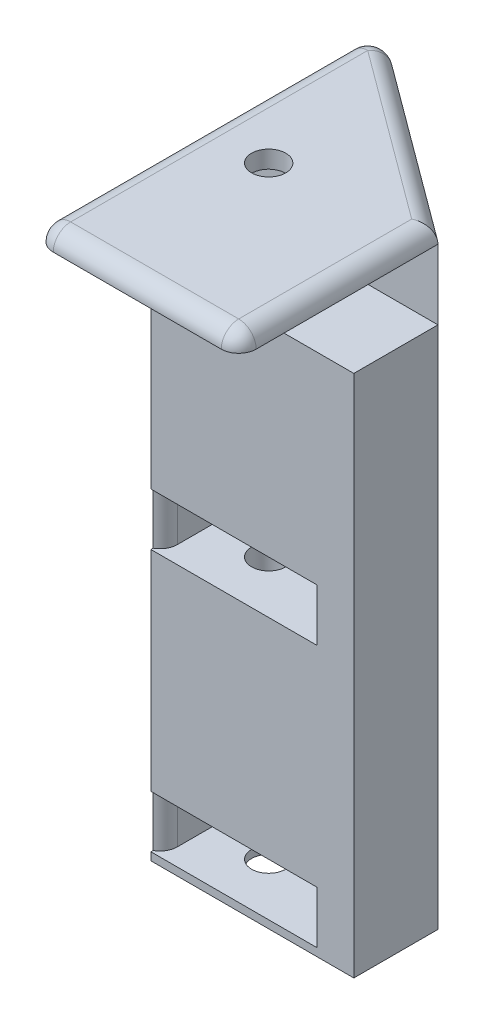
SolidWorks part; units mm, degrees
material "PLA/ABS"
ref_plane "Front Plane" through (0, 0, 0) normal (0, 0, 1) x (1, 0, 0)
ref_plane "Top Plane" through (0, 0, 0) normal (0, 1, 0) x (1, 0, 0)
ref_plane "Right Plane" through (0, 0, 0) normal (1, 0, 0) x (0, 0, -1)
other "Bounding Box"
ref_plane "Default Plane" through (-8.9266, -12.7485, 0) normal (-0.1736, 0.9848, 0) x (0.9848, 0.1736, 0)
sketch "Sketch1" plane through (0, 0, 0) normal (0, 1, 0) x (1, 0, 0)
  line B0 (-13.2357, 21.8055) -> (-13.2357, -16.2945)
  line B1 (-13.2357, -16.2945) -> (16.2964, -16.2945)
  line B2 (16.2964, -16.2945) -> (16.2964, 0)
  line B3 (16.2964, 0) -> (-13.2357, 21.8055)
  line B4 (16.2964, 0) -> (-13.2357, 0)
sketch_block_instance "Inter mount mount-1"
sketch_block "Inter mount mount" parameters "D1"=38.1
extrude "Boss-Extrude1" add sketch "Sketch1" along normal blind 6.35 contours B4 B3 B0 | B2 B4 B0 B1 region at (-3.3916, 0, -7.2685) region at (1.5304, 0, 8.1472)
extrude "Boss-Extrude2" add sketch "Sketch1<3>" against normal blind 82.55 contours B4 B3 B0 region at (-3.3916, 0, -7.2685)
sketch "Sketch1<3>" plane through (0, 0, 0) normal (0, 1, 0) x (1, 0, 0) same geometry as "Sketch1"
sketch "Sketch2" plane through (0, 0, 0) normal (0, -1, 0) x (-1, 0, 0)
  line L0 (13.2357, 0) -> (-16.2964, 0)
  line L5 (13.2357, 0) -> (13.2357, -16.2945)
  line L6 (-16.2964, 0) -> (-16.2964, -16.2945)
  line L7 (13.2357, -16.2945) -> (-16.2964, -16.2945)
  line L8 (13.2357, -16.2945) -> (-16.2964, -16.2945) construction
extrude "Cut-Extrude1" cut sketch "Sketch2" against normal blind 3.175
sketch "Sketch4" plane through (0, 6.35, 0) normal (0, 1, 0) x (1, 0, 0)
  line L0 (16.2964, -16.2945) -> (16.2964, 0) construction
  line L1 (-13.2357, -16.2945) -> (16.2964, -16.2945)
  line L2 (-13.2357, -16.2945) -> (-13.2357, -28.9945)
  line L3 (-13.2357, -28.9945) -> (16.2964, -28.9945)
  line L4 (16.2964, -16.2945) -> (16.2964, -28.9945)
  dimension "D1" = 12.7
extrude "Boss-Extrude3" add sketch "Sketch4" against normal up to surface (3.175 mm away) up to face at (1.5304, 3.175, 8.1472)
sketch3d "3DSketch1" plane through (0, 0, 0) normal (0, 0, 1) x (1, 0, 0)
  dimension "D1" = 3.175
sketch "Sketch7" plane through (3.8639, 0, -5.2331) normal (0.594, 0, -0.8045) x (-0.8045, 0, -0.594)
  line L0 (-13.11, -82.55) -> (-13.11, 3.175) construction
  line L1 (-13.11, -73.787) -> (23.6, -73.787)
  line L2 (-13.11, -73.787) -> (-13.11, -81.407)
  line L3 (-13.11, -81.407) -> (23.6, -81.407)
  line L4 (23.6, -73.787) -> (23.6, -81.407)
  line L5 (23.6, 6.35) -> (23.6, -82.55) construction
  line L6 (-13.11, -82.55) -> (23.6, -82.55) construction
  dimension "D1" = 1.143
  dimension "D2" = 7.62
extrude "Cut-Extrude4" cut sketch "Sketch7" against normal blind 13.589 contours L2 L1 L4 L3
sketch "Sketch8" plane through (3.8639, 0, -5.2331) normal (0.594, 0, -0.8045) x (-0.8045, 0, -0.594)
  line L0 (-13.11, -82.55) -> (-13.11, 3.175) construction
  line L1 (-13.11, -43.307) -> (23.6, -43.307)
  line L2 (-13.11, -43.307) -> (-13.11, -35.687)
  line L3 (-13.11, -35.687) -> (23.6, -35.687)
  line L4 (23.6, -43.307) -> (23.6, -35.687)
  line L5 (23.6, 6.35) -> (23.6, -82.55) construction
  line L7 (-8.81, -73.787) -> (9.5942, -73.787) construction
  dimension "D1" = 30.48
  dimension "D2" = 7.62
extrude "Cut-Extrude5" cut sketch "Sketch8" against normal blind 13.589
sketch "Sketch9" plane through (0, 0, 0) normal (0, 0, 1) x (1, 0, 0)
  line L1 (-13.2357, -82.55) -> (16.2964, -82.55)
  line L2 (-13.2357, -82.55) -> (-13.2357, 3.175)
  line L3 (-13.2357, 3.175) -> (16.2964, 3.175)
  line L4 (16.2964, -82.55) -> (16.2964, 3.175)
  line L5 (-11.9261, -43.307) -> (10.9513, -43.307)
  line L6 (-11.9261, -43.307) -> (-11.9261, -35.687)
  line L7 (-11.9261, -35.687) -> (10.9513, -35.687)
  line L8 (10.9513, -43.307) -> (10.9513, -35.687)
  line L9 (-11.9261, -81.407) -> (10.9513, -81.407)
  line L10 (-11.9261, -81.407) -> (-11.9261, -73.787)
  line L11 (-11.9261, -73.787) -> (10.9513, -73.787)
  line L12 (10.9513, -81.407) -> (10.9513, -73.787)
  line L13 (-13.2357, 3.175) -> (16.2964, 3.175)
  line L14 (-13.2357, 3.175) -> (-13.2357, -6.35)
  line L15 (-13.2357, -6.35) -> (16.2964, -6.35)
  line L16 (16.2964, 3.175) -> (16.2964, -6.35)
  line M9 (10.9513, -43.307) -> (-11.9261, -43.307)
  line M10 (-11.9261, -43.307) -> (-11.9261, -35.687)
  line M11 (-11.9261, -35.687) -> (10.9513, -35.687)
  line M12 (10.9513, -35.687) -> (10.9513, -43.307)
  line M13 (10.9513, -81.407) -> (-11.9261, -81.407)
  line M14 (-11.9261, -81.407) -> (-11.9261, -73.787)
  line M15 (-11.9261, -73.787) -> (10.9513, -73.787)
  line M16 (10.9513, -73.787) -> (10.9513, -81.407)
  line M17 (16.2964, -82.55) -> (16.2964, 3.175)
  line M20 (-13.2357, -82.55) -> (16.2964, -82.55)
  dimension "D1" = 9.525
extrude "Boss-Extrude5" add sketch "Sketch9" along normal blind 12.2428 contours L15 L2 M20 M17 M16 M13 M14 M15 M12 M9 M10 M11 region at (-12.4185, -44.45, 0)
sketch "Sketch10" plane through (0, -82.55, 0) normal (0, -1, 0) x (-1, 0, 0)
  line L0 (13.2357, 21.8055) -> (13.2357, -12.2428) construction
  line L1 (13.2357, -12.2428) -> (-16.2964, -12.2428) construction
  circle A0 centre (3.7107, -4.6228) radius 2.4892
  dimension "D1" = 4.9784
  dimension "D3" = 7.62
  dimension "D2" = 9.525
extrude "Cut-Extrude6" cut sketch "Sketch10" against normal through all both and the other way through all
fillet "Fillet2" radius 2.54 7 edges at (-13.2357, -38.1, -21.8055) (-11.9261, -77.597, 0) (-11.9261, -77.597, 12.2428) (-11.9261, -39.497, 12.2428) (-11.9261, -39.497, 0) (-13.2357, 4.7625, 28.9945) (16.2964, 4.7625, 28.9945)
fillet "Fillet3" radius 2.54 7 edges at (16.2964, 6.35, 13.2272) (15.5525, 6.35, 28.2505) (1.5304, 6.35, 28.9945) (-12.4917, 6.35, 28.2505) (-13.2357, 6.35, 4.8409) (-11.8401, 6.35, -19.0403) (3.5547, 6.35, -9.408)
mirror "Mirror1" [suppressed] of bodies 114
delete or keep bodies "Body-Delete/Keep 1" [suppressed] type delete bodies bodies 114
sketch "Sketch11" plane through (5.7498, 0, -7.7872) normal (0.594, 0, -0.8045) x (-0.8045, 0, -0.594)
  circle A0 centre (-11.0457, -62.23) radius 1.5875
  circle A1 centre (1.6543, -62.23) radius 1.5875
  circle A2 centre (14.3543, -62.23) radius 1.5875
  circle A3 centre (-11.0457, -36.83) radius 1.5875
  circle A4 centre (1.6543, -36.83) radius 1.5875
  circle A5 centre (14.3543, -36.83) radius 1.5875
  circle A6 centre (-11.0457, -11.43) radius 1.5875
  circle A7 centre (1.6543, -11.43) radius 1.5875
  circle A8 centre (14.3543, -11.43) radius 1.5875
  dimension "D1" = 3
  dimension "D2" = 3
extrude "Cut-Extrude7" cut sketch "Sketch11" against normal blind 6.35 and the other way blind 2.54
sketch "Sketch12" plane through (16.2964, 0, 0) normal (1, 0, 0) x (0, 0, -1)
  line L1 (0, 3.81) -> (-28.9945, 3.81)
  line L2 (0, 3.81) -> (0, 3.175)
  line L3 (0, 3.175) -> (-28.9945, 3.175)
  line L4 (-28.9945, 3.81) -> (-28.9945, 3.175)
extrude "Cut-Extrude8" cut sketch "Sketch12" against normal through all both and the other way through all
